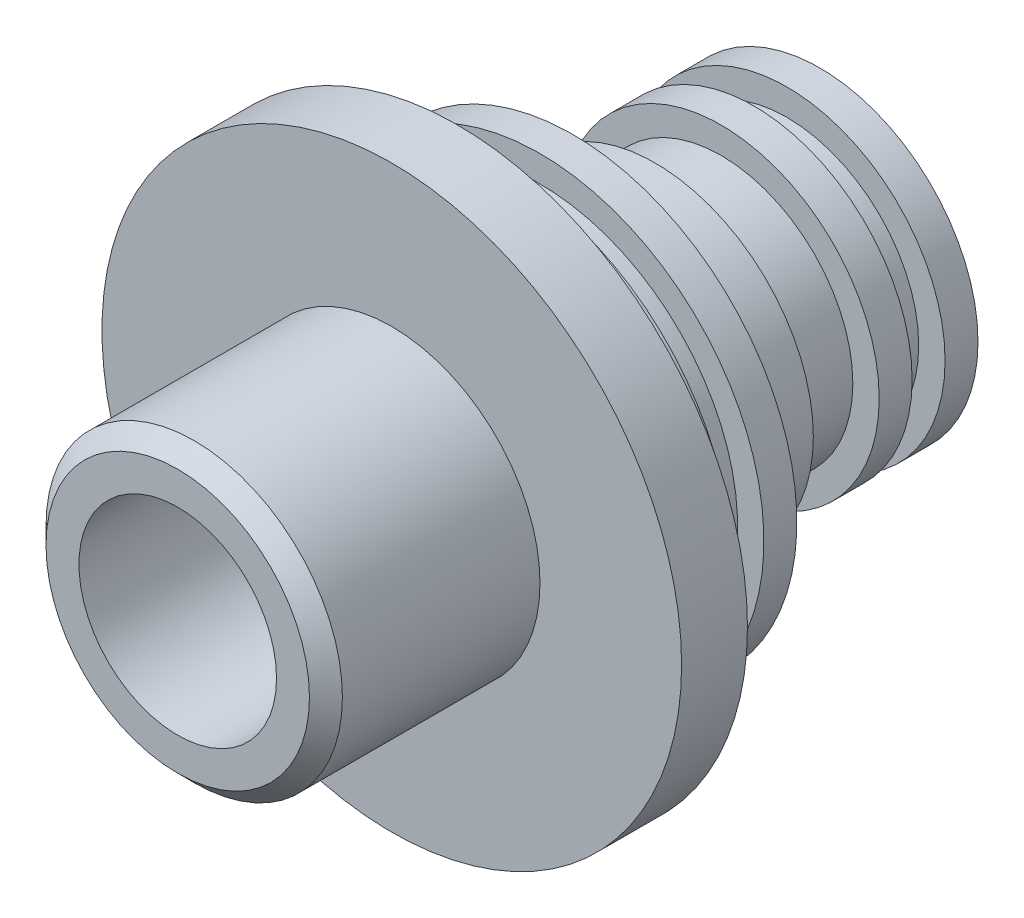
SolidWorks part; units mm, degrees
ref_plane "Front Plane" through (0, 0, 0) normal (0, 0, 1) x (1, 0, 0)
ref_plane "Top Plane" through (0, 0, 0) normal (0, 1, 0) x (1, 0, 0)
ref_plane "Right Plane" through (0, 0, 0) normal (1, 0, 0) x (0, 0, -1)
sketch "Sketch1" plane through (0, 0, 0) normal (0, 0, 1) x (1, 0, 0)
  circle A0 centre (0, 0) radius 8.8
  circle A1 centre (0, 0) radius 3
extrude "Boss-Extrude1" add sketch "Sketch1" along normal blind 19.5
sketch "Sketch2" plane through (0, 0, 19.5) normal (0, 0, 1) x (1, 0, 0)
  circle A0 centre (0, 0) radius 4.5
extrude "Cut-Extrude1" cut sketch "Sketch2" against normal blind 6.5 flip side to cut
sketch "Sketch3" plane through (0, 0, 0) normal (0, 0, -1) x (-1, 0, 0)
  circle A0 centre (0, 0) radius 6.8
extrude "Cut-Extrude2" cut sketch "Sketch3" against normal offset from surface (11 mm away) 2 flip side to cut up to face at (4.5, 0, 13)
sketch "Sketch5" plane through (0, 0, 0) normal (0, 0, -1) x (-1, 0, 0)
  circle A0 centre (0, 0) radius 4.8
extrude "Cut-Extrude3" cut sketch "Sketch5" against normal blind 7.5 flip side to cut
sketch "Sketch4" plane through (0, 0, 7.5) normal (0, 0, -1) x (-1, 0, 0)
  circle A1 centre (0, 0) radius 6
extrude "Cut-Extrude4" cut sketch "Sketch4" against normal blind 1 from offset 1 flip side to cut offset against normal yes
sketch "Sketch6" plane through (0, 0, 0) normal (0, 0, -1) x (-1, 0, 0)
  circle A0 centre (0, 0) radius 4
extrude "Cut-Extrude5" cut sketch "Sketch6" against normal blind 1 from offset 1 flip side to cut offset against normal yes
extrude "Cut-Extrude6" cut sketch "Sketch6<2>" against normal blind 2 from offset 3 flip side to cut offset against normal yes
sketch "Sketch6<2>" plane through (0, 0, 0) normal (0, 0, -1) x (-1, 0, 0) same geometry as "Sketch6"
chamfer "Chamfer1" distance 0.5 angle 45 1 edges at (4.5, 0, 19.5)
